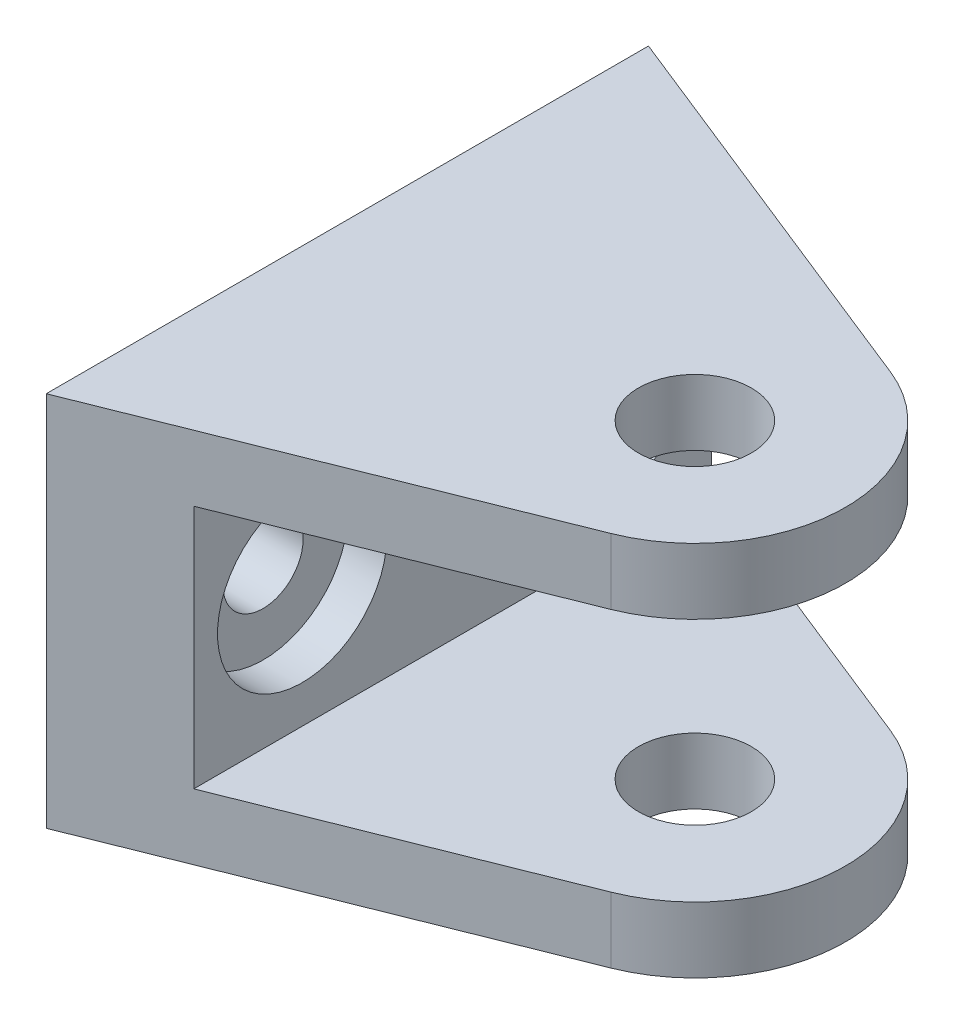
SolidWorks part; units mm, degrees
ref_plane "Front Plane" through (0, 0, 0) normal (0, 0, 1) x (1, 0, 0)
ref_plane "Top Plane" through (0, 0, 0) normal (0, 1, 0) x (1, 0, 0)
ref_plane "Right Plane" through (0, 0, 0) normal (1, 0, 0) x (0, 0, -1)
sketch "Sketch1" plane through (0, 0, 0) normal (0, 0, 1) x (1, 0, 0)
  line L0 (0, 0) -> (42.0157, 0)
  line L1 (42.0157, 0) -> (42.0157, 5.5499)
  line L2 (42.0157, 5.5499) -> (8.89, 5.5499)
  line L3 (8.89, 5.5499) -> (8.89, 26.2001)
  line L4 (8.89, 26.2001) -> (42.0157, 26.2001)
  line L5 (42.0157, 26.2001) -> (42.0157, 31.75)
  line L6 (42.0157, 31.75) -> (0, 31.75)
  line L7 (0, 31.75) -> (0, 0)
  line L8 (29.3157, 31.75) -> (29.3157, 0) construction
  dimension "D1" = 31.75
  dimension "D2" = 20.6502
  dimension "D3" = 12.7
  dimension "D4" = 8.89
extrude "Boss-Extrude1" add sketch "Sketch1" along normal blind 50.8
sketch "Sketch2" plane through (8.89, 0, 0) normal (1, 0, 0) x (0, 0, -1)
  line L0 (-25.4, 31.75) -> (-25.4, 0) construction
  line L1 (-50.8, 31.75) -> (0, 31.75) construction
  line L2 (-50.8, 0) -> (0, 0) construction
  line L3 (-38.1, 15.875) -> (-12.7, 15.875) construction
  circle A0 centre (-38.1, 15.875) radius 3.175
  circle A1 centre (-12.7, 15.875) radius 3.175
  point P6 (-38.1, 15.875)
  point P7 (-12.7, 15.875)
  point P8 (-25.4, 15.875)
  point P15 (-12.7, 15.875)
  point P17 (-38.1, 15.875)
  dimension "D2" = 6.35
  dimension "D1" = 25.4
hole_wizard "CBORE for 1/4 Binding Head Machine Screw1" positions "Sketch2" profile "Sketch7" counterbore size "1/4" standard "ANSI Inch" end condition through all
sketch "Sketch7" plane through (8.89, 15.875, 38.1) normal (0, 1, 0) x (0, 0, -1)
  line L0 (0, 0) -> (0, 8.89)
  line L1 (0, 8.89) -> (3.3782, 8.89)
  line L3 (3.3782, 8.89) -> (3.3782, 3.302)
  line L4 (3.3782, 3.302) -> (7.1437, 3.302)
  line L5 (7.1437, 3.302) -> (7.1437, 0)
  line L7 (7.1437, 0) -> (0, 0)
  line L11 (0, -6.35) -> (0, 107.95) construction
  dimension "Thru Hole Dia." = 6.7564
  dimension "Thru Hole Depth" = 8.89
  dimension "C'Bore Dia." = 14.2875
  dimension "C'Bore Depth" = 3.302
sketch "Sketch3" plane through (0, 0, 0) normal (0, -1, 0) x (1, 0, 0)
  line L0 (34701.1242, 25.4) -> (-34766.6696, 25.4) construction
  circle A0 centre (29.3157, 25.4) radius 4.7625
  dimension "D1" = 9.525
extrude "Spherical Holes " cut sketch "Sketch3" against normal up to surface (31.75 mm away) up to face at (21.0078, 31.75, 25.4)
sketch "Sketch4" plane through (0, 31.75, 0) normal (0, 1, 0) x (1, 0, 0)
  line L0 (42.0157, -50.8) -> (42.0157, 0) construction
  line L1 (0, 0) -> (34.031, -13.6078)
  line L2 (0, -50.8) -> (34.031, -37.1922)
  line L5 (0, 0) -> (0, -50.8)
  arc A0 (34.031, -37.1922) -> (34.031, -13.6078) centre (29.3157, -25.4) ccw
extrude "Rounding" cut sketch "Sketch4" against normal up to surface (31.75 mm away) flip side to cut up to face at (29.3157, 0, 20.6375)
